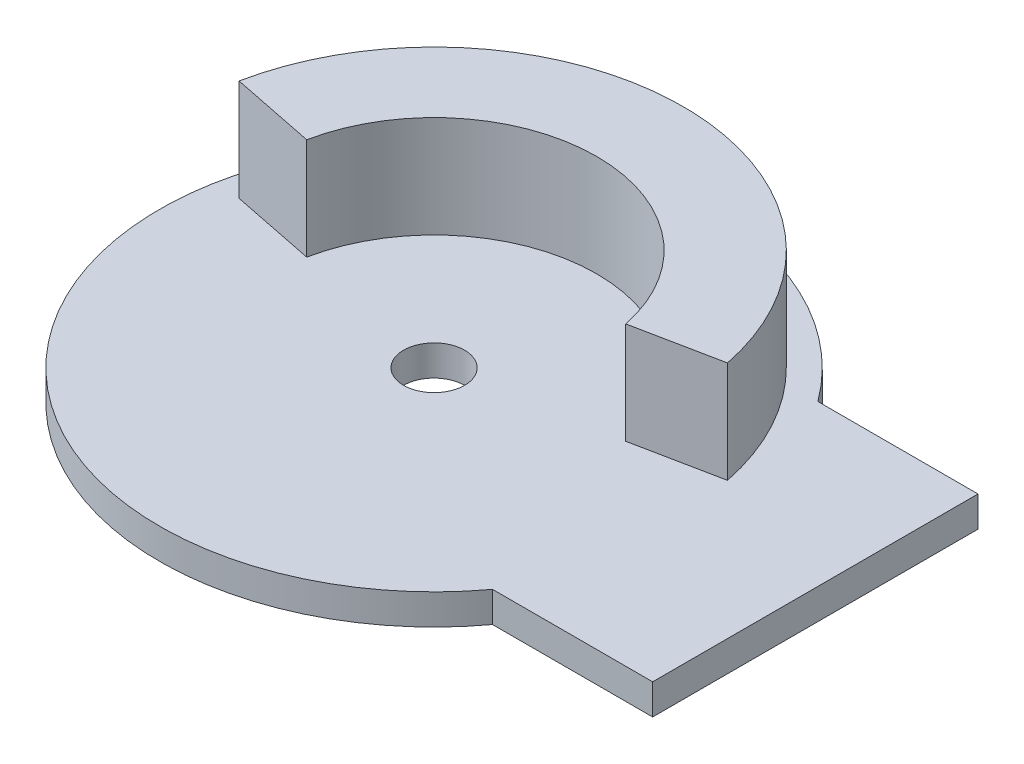
SolidWorks part; units mm, degrees
ref_plane "Front Plane" through (0, 0, 0) normal (0, 0, 1) x (1, 0, 0)
ref_plane "Top Plane" through (0, 0, 0) normal (0, 1, 0) x (1, 0, 0)
ref_plane "Right Plane" through (0, 0, 0) normal (1, 0, 0) x (0, 0, -1)
sketch "Sketch1" plane through (0, 0, 0) normal (0, 1, 0) x (1, 0, 0)
  line L0 (-55, 0) -> (55, 0) construction
  line L1 (-24.0173, 4.8395) -> (-20.7184, 21.2108) construction
  line L2 (-24.0173, 4.8395) -> (-15.6847, 3.1605)
  line L3 (0, -55) -> (0, 55) construction
  line L4 (24.0173, 4.8395) -> (15.6847, 3.1605)
  line L5 (-23.9844, 5) -> (23.9844, 5) construction
  circle A0 centre (0, 0) radius 16 construction
  circle A1 centre (0, 0) radius 24.5 construction
  arc A2 (-24.0173, 4.8395) -> (24.0173, 4.8395) centre (0, 0) cw
  arc A3 (-15.6847, 3.1605) -> (15.6847, 3.1605) centre (0, 0) cw
  point P20 (-19.851, 4)
  dimension "D1" = 32
  dimension "D2" = 49
  dimension "D3" = 1
  dimension "D4" = 5
extrude "Boss-Extrude1" add sketch "Sketch1" along normal blind 10 contours A2 L4 A3 L2
sketch "Sketch2" plane through (0, 0, 0) normal (0, -1, 0) x (1, 0, 0)
  line L1 (37.5, -16) -> (37.5, 16)
  line L3 (21.7486, -16) -> (37.5, -16)
  line L5 (21.7486, 16) -> (37.5, 16)
  line L6 (0, -55) -> (0, 55) construction
  circle A1 centre (0, 0) radius 27 construction
  circle A2 centre (0, 0) radius 3
  arc A3 (0, -27) -> (0, 27) centre (0, 0) cw
  circle A4 centre (0, 0) radius 16 construction
  arc A5 (21.7486, -16) -> (0, -27) centre (0, 0) cw
  arc A6 (0, 27) -> (21.7486, 16) centre (0, 0) cw
  dimension "D1" = 54
  dimension "D2" = 6
  dimension "D3" = 37.5
extrude "Boss-Extrude2" add sketch "Sketch2" along normal blind 3
sketch "Sketch4" plane through (0, 0, 0) normal (0, 1, 0) x (1, 0, 0)
  line L0 (37.5, -16) -> (21.7486, -16) construction
  line L1 (37.5, -16) -> (35, -16)
  line L2 (37.5, -16) -> (37.5, 16)
  line L3 (37.5, 16) -> (35, 16)
  line L4 (35, -16) -> (35, 16)
  line L5 (21.7486, 16) -> (37.5, 16) construction
  dimension "D1" = 2.5
  dimension "D2" = 35
extrude "Boss-Extrude3" [suppressed] add sketch "Sketch4" along normal blind 60
sketch "Sketch5" [suppressed] plane through (37.5, 0, 0) normal (1, 0, 0) x (0, 0, -1)
  line L0 (16, 60) -> (-16, -2.5) construction
  line L1 (-16, -2.5) -> (16, -2.5) construction
  line L2 (16, -2.5) -> (-16, 60) construction
  circle A0 centre (0, 28.75) radius 5
  dimension "D1" = 10
extrude "Cut-Extrude1" [suppressed] cut sketch "Sketch5" against normal blind 10
ref_axis "Axis1" [suppressed] through (35, 28.75, 0) along (1, 0, 0)
ref_plane "Plane1" [suppressed] through (0, 28.75, 0) normal (0, 1, 0) x (1, 0, 0)
